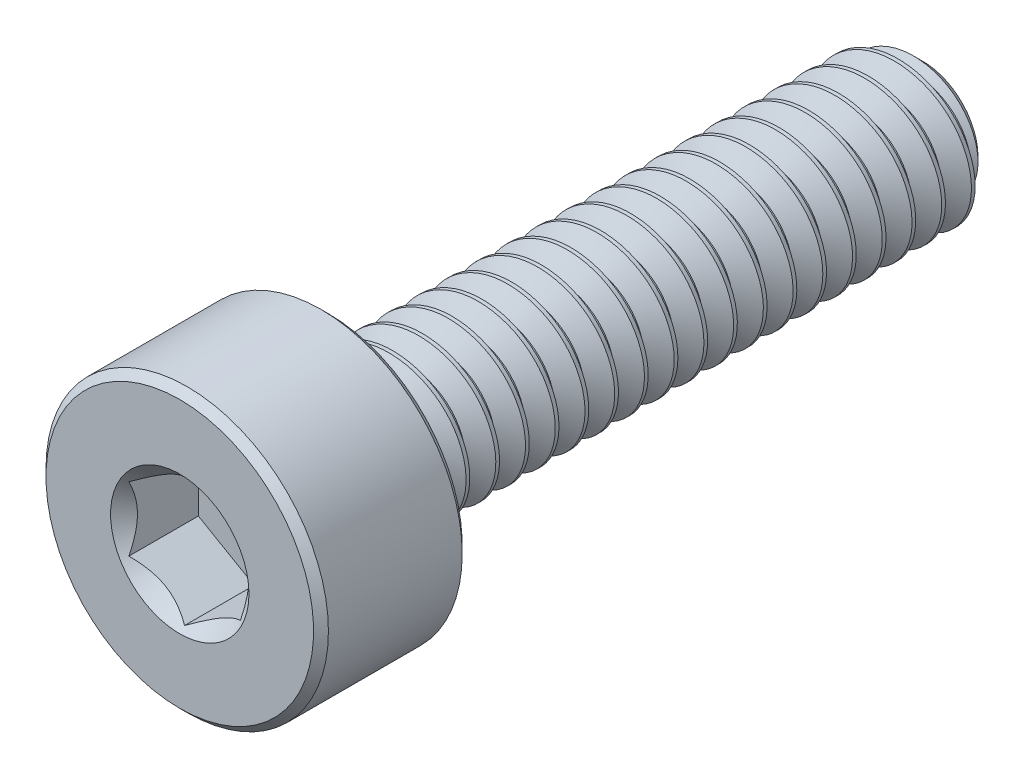
SolidWorks part; units mm, degrees
ref_plane "Front Plane" through (0, 0, 0) normal (0, 0, 1) x (1, 0, 0)
ref_plane "Top Plane" through (0, 0, 0) normal (0, 1, 0) x (1, 0, 0)
ref_plane "Right Plane" through (0, 0, 0) normal (1, 0, 0) x (0, 0, -1)
sketch "Sketch1" plane through (0, 0, 0) normal (1, 0, 0) x (0, 0, -1)
  line L0 (-5, 0) -> (5, 0) construction
  line L1 (5, 0) -> (5, 0.7402) construction
  line L2 (5, 0.7402) -> (4.7402, 1) construction
  line L3 (4.7402, 1) -> (4.7, 1) construction
  line L4 (4.7, 1) -> (-3, 1) construction
  line L5 (-3, 1) -> (-3, 1.9) construction
  line L6 (-3, 1.9) -> (-5, 1.9) construction
  line L7 (-5, 1.9) -> (-5, 0) construction
  line L8 (5, 0.7402) -> (5, 1) construction
  line L9 (4.975, 1.0433) -> (5.175, 0.6969) construction
  line L10 (5.175, 0.6969) -> (5.375, 1.0433) construction
  line L11 (5.375, 1.0433) -> (4.975, 1.0433) construction
  line L12 (5.175, 1.0433) -> (5.175, 1) construction
  line L13 (5.175, 0.6969) -> (5.175, 0.7402) construction
  line L14 (5.15, 0.7402) -> (5.2, 0.7402) construction
  line L15 (5, 1) -> (5.35, 1) construction
  line L16 (4.9875, 1.0217) -> (5.3625, 1.0217) construction
  line L17 (5, 0) -> (5, -1) construction
  line L18 (-3.1, 1.9) -> (-3, 1.8) construction
  line L19 (-4.9, 1.9) -> (-5, 1.8) construction
  line L20 (-3, 1) -> (-3, 0) construction
  line L21 (-3, 0.5) -> (-0.3333, 0.5) construction
  line L22 (-0.3333, 0.5) -> (2.3333, 0.5) construction
  line L23 (2.3333, 0.5) -> (5, 0.5) construction
  line L24 (-0.3333, 0.5) -> (-0.3333, 1) construction
  line L25 (-0.3333, 1) -> (-0.3333, 1.9) construction
  line L26 (2.3333, 0.5) -> (2.3333, 1.9) construction
  point P0 (-5, 0.75)
  point P3 (4, 1)
  point P4 (0, 0)
  point P18 (2.3333, 1)
  point P22 (5.175, 0.7402)
  point P24 (4.7, 1)
  point P25 (5.175, 1)
  point P28 (5.175, 1.0217)
  point P29 (4, -1)
  point P30 (-0.3333, 1)
  point P31 (-4, 1.9)
  point P37 (-3.35, 1.9)
  point P38 (-4.85, 1.9)
  point P45 (-0.3333, 0.5)
  point P46 (2.3333, 0.5)
  dimension "D2" = 0.05
  dimension "D7" = 0.1
  dimension "D8" = 0.1
  dimension "D9" = 0.1
  dimension "D10" = 0.05
  dimension "D11" = 0.25
  dimension "Drive Size" = 1.5
  dimension "Head Diameter" = 3.8
  dimension "Head Height" = 2
  dimension "Thread Pitch" = 0.4
  dimension "Thread Dia" = 2
  dimension "Length" = 8
  dimension "D12" = 0.3
  dimension "D4" = 1
  dimension "D3" = 45
sketch "Sketch2" plane through (0, 0, 0) normal (1, 0, 0) x (0, 0, -1)
  line L0 (-5, 0) -> (-5, 1.8)
  line L1 (-4.9, 1.9) -> (-3.1, 1.9)
  line L2 (-3, 1.8) -> (-3, 1.1)
  line L4 (4.7402, 1) -> (5, 0.7402)
  line L5 (5, 0.7402) -> (5, 0)
  line L6 (-3, 1.9) -> (-5, 1.9) construction
  line L7 (5, 0) -> (-5, 0)
  line L8 (-4.9, 1.9) -> (-5, 1.8) construction
  line L10 (-4.9, 1.9) -> (-5, 1.8)
  line L14 (-3.1, 1.9) -> (-3, 1.8) construction
  line L16 (-3.1, 1.9) -> (-3, 1.8)
  line L17 (-3, 1) -> (-3, 1.9) construction
  line L19 (-2.9, 1) -> (4.7402, 1)
  line L20 (4.7, 1) -> (-3, 1) construction
  arc A1 (-3, 1.1) -> (-2.9, 1) centre (-2.9, 1.1) ccw
  dimension "D3" = 0.1
revolve "Revolve1" add sketch "Sketch2" angle 360 about L7
sketch "Sketch3" plane through (0, 0, 5) normal (0, 0, 1) x (1, 0, 0)
  line L1 (0.75, -0.433) -> (0.75, 0.433)
  line L2 (0.75, 0.433) -> (0, 0.866)
  line L3 (0, 0.866) -> (-0.75, 0.433)
  line L4 (-0.75, 0.433) -> (-0.75, -0.433)
  line L5 (-0.75, -0.433) -> (0, -0.866)
  line L6 (0, -0.866) -> (0.75, -0.433)
  circle A0 centre (0, 0) radius 0.75 construction
  circle A1 centre (0, 0) radius 1.9 construction
  circle A2 centre (0, 0) radius 1.9 construction
  circle A3 centre (0, 0) radius 0.866 construction
  point P13 (0, 0)
  dimension "D1" = 1.7321
extrude "Cut-Extrude1" cut sketch "Sketch3" against normal offset from surface (1 mm away) 1 up to face at (0, 1.8, 3)
sketch "Sketch4" plane through (0, 0, 5) normal (0, 0, 1) x (1, 0, 0)
  circle A0 centre (0, 0) radius 0.931
  dimension "D1" = 1.862
extrude "Cut-Extrude2" cut sketch "Sketch4" against normal up to vertex (1 mm away) draft 45 up to point (0, 1.9, 4)
sketch "Sketch11" plane through (0, 0, 0) normal (1, 0, 0) x (0, 0, -1)
  line L0 (-5, 0) -> (5, 0) construction
  line L1 (-5, 0) -> (5, 0) construction
  line L2 (-1.5, 0) -> (-1.5, 1) construction
  line L3 (4.7, 1) -> (-3, 1) construction
  line L4 (3.5, 0) -> (3.5, 1) construction
  line L6 (5, 0.7402) -> (5, 1) construction
  point P2 (-1.5, 0)
  point P3 (3.5, 0)
  dimension "D1" = 1.5
  dimension "D2" = 1.5
sketch "Sketch6" plane through (0, 0, -5) normal (0, 0, -1) x (-1, 0, 0)
  circle A0 centre (0, 0) radius 1
curve "Helix/Spiral1" pitch 0.4 height 8.4 radius 1 centre (0, 0, -5) axis (0, 0, 1) start towards (0, 1, 0)
sketch "Sketch10" plane through (0, 0, 0) normal (1, 0, 0) x (0, 0, -1)
  line L0 (-2.9, -1.9) -> (-2.9, 1.9)
  line L5 (-5, 0) -> (5, 0) construction
  line L6 (-2.9, 1) -> (-2.9, -1) construction
  point P3 (-2.9, 0)
split "Split1" trim tools "Sketch10" bodies to split 106 resulting bodies 114 115
sketch "Sketch7" plane through (0, 0, 0) normal (1, 0, 0) x (0, 0, -1)
  line L0 (4.9875, 1.0217) -> (5.3625, 1.0217)
  line L1 (5.3625, 1.0217) -> (5.2, 0.7402)
  line L2 (5.2, 0.7402) -> (5.15, 0.7402)
  line L3 (5.15, 0.7402) -> (4.9875, 1.0217)
sweep "Cut-Sweep1" cut profiles "Sketch7" path "Helix/Spiral1" align with end faces yes
sketch "Sketch8" plane through (0, 0, 0) normal (1, 0, 0) x (0, 0, -1)
  line L0 (-3, 0) -> (-3, 1)
  line L1 (-2.9, -1) -> (-2.9, 1) construction
  line L2 (-3, 1) -> (-2.9, 1)
  line L4 (-2.9, 1) -> (-2.3226, 0)
  line L5 (-2.3226, 0) -> (-3, 0)
  line L6 (4.7, 1) -> (-3, 1) construction
  line L7 (-5, 0) -> (5, 0) construction
  dimension "D1" = 60
revolve "Revolve2" add sketch "Sketch8" angle 360 about L5
equation "\"D2@Sketch1\" = \"Thread Pitch@Sketch1\" / 8"
equation "\"D4@Helix/Spiral1\" = \"Thread Pitch@Sketch1\""
equation "\"D7@Sketch1\" = \"Head Height@Sketch1\" * .05"
equation "\"D8@Sketch1\"=\"D7@Sketch1\""
equation "\"D9@Sketch1\"=\"D7@Sketch1\""
equation "\"D10@Sketch1\"=\"D7@Sketch1\"/2"
equation "\"D11@Sketch1\"=\"D10@Sketch1\"*5"
equation "\"D4@Sketch1\"=\"Thread Pitch@Sketch1\"*2.5"
equation "\"D12@Sketch1\"=\"Thread Pitch@Sketch1\"*.75"
equation "\"D3@Helix/Spiral1\"=\"Length@Sketch1\"+\"Thread Pitch@Sketch1\""
equation "\"D3@Sketch2\"=\"Thread Dia@Sketch1\"*0.05"
equation "\"D1@Sketch11\"=\"Length@Sketch1\"*0.1875"
equation "\"D2@Sketch11\"=\"D1@Sketch11\""
equation "\"D1@Sketch4\"=\"D1@Sketch3\"*1.075"
